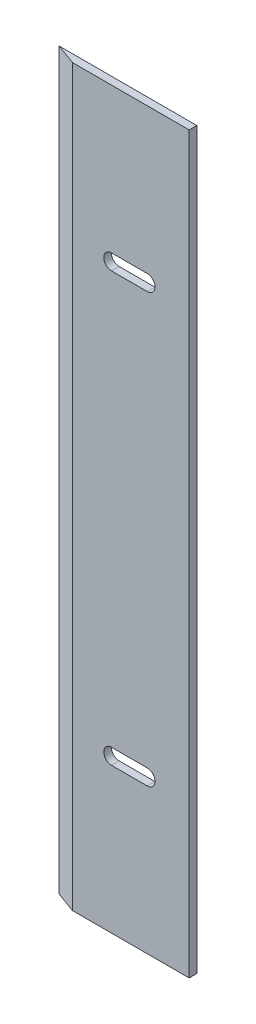
SolidWorks part; units mm, degrees
ref_plane "Спереди" through (0, 0, 0) normal (0, 0, 1) x (1, 0, 0)
ref_plane "Сверху" through (0, 0, 0) normal (0, 1, 0) x (1, 0, 0)
ref_plane "Справа" through (0, 0, 0) normal (1, 0, 0) x (0, 0, -1)
sketch "Эскиз1" plane through (0, 0, 0) normal (0, 0, 1) x (1, 0, 0)
  line L1 (-48.4463, 48) -> (-66.4463, 48)
  line L2 (-48.4463, 48) -> (-48.4463, -48)
  line L3 (-48.4463, -48) -> (-66.4463, -48)
  line L4 (-66.4463, 48) -> (-66.4463, -48)
  line L7 (-48.4463, 0) -> (-59.9363, 0) construction
  point P7 (0, 0)
  point P8 (0, 0)
extrude "Бобышка-Вытянуть1" add sketch "Эскиз1" along normal blind 1 contours L1 L4 L3 L2 region at (-57.4463, 0, 0)
sketch "Эскиз2" plane through (0, 48, 0) normal (0, 1, 0) x (1, 0, 0)
  line L0 (-66.4463, 0) -> (-63.6988, -1)
  line L1 (-48.4463, -1) -> (-66.4463, -1) construction
  line L2 (-48.4463, 0) -> (-66.4463, 0) construction
  line L4 (-63.6988, -1) -> (-66.4463, -1)
  line L5 (-66.4463, -1) -> (-66.4463, 0)
  dimension "D1" = 20
extrude "Вырез-Вытянуть1" cut sketch "Эскиз2" against normal through all
sketch "Эскиз3" plane through (0, 0, 0) normal (0, 0, -1) x (-1, 0, 0)
  circle A0 centre (56.2632, -28.0157) radius 1
  circle A1 centre (56.2632, 27.9843) radius 1
sketch "Эскиз4" plane through (0, 0, 1) normal (0, 0, 1) x (1, 0, 0)
  line L0 (-58.5951, 27.9843) -> (-53.9313, 27.9843) construction
  line L1 (-58.5951, 29.0021) -> (-53.9313, 29.0021)
  line L2 (-58.5951, 26.9665) -> (-53.9313, 26.9665)
  line L3 (-48.4463, 0) -> (-63.6988, 0) construction
  line L4 (-48.4463, 48) -> (-48.4463, -48) construction
  line L5 (-63.6988, -48) -> (-63.6988, 48) construction
  line L6 (-58.5951, -27.9843) -> (-53.9313, -27.9843) construction
  line L7 (-58.5951, -29.0021) -> (-53.9313, -29.0021)
  line L8 (-58.5951, -26.9665) -> (-53.9313, -26.9665)
  arc A0 (-58.5951, 29.0021) -> (-58.5951, 26.9665) centre (-58.5951, 27.9843) ccw
  arc A1 (-53.9313, 26.9665) -> (-53.9313, 29.0021) centre (-53.9313, 27.9843) ccw
  arc A2 (-58.5951, -29.0021) -> (-58.5951, -26.9665) centre (-58.5951, -27.9843) cw
  arc A3 (-53.9313, -26.9665) -> (-53.9313, -29.0021) centre (-53.9313, -27.9843) cw
  point P2 (-56.2632, 27.9843)
  point P16 (-56.2632, -27.9843)
extrude "Вырез-Вытянуть2" cut sketch "Эскиз4" against normal blind 10
